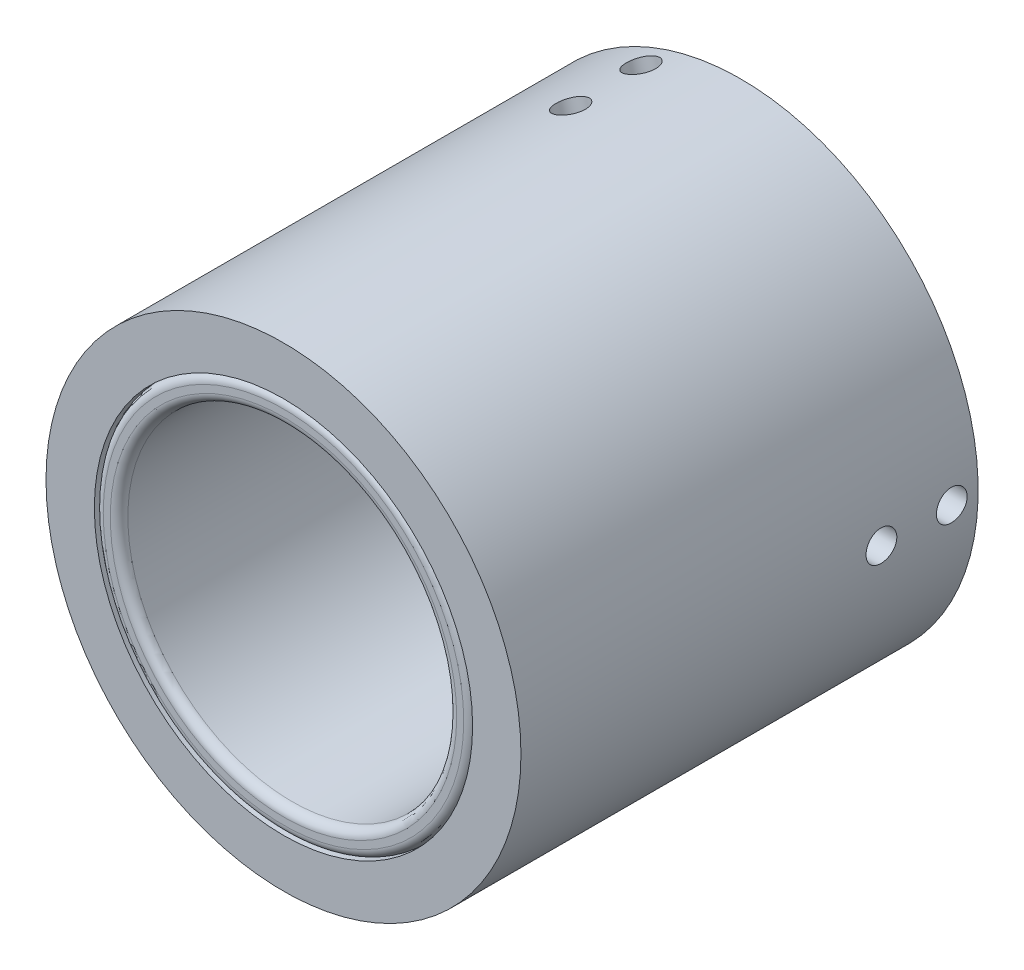
SolidWorks part; units mm, degrees
ref_plane "Plan de face" through (0, 0, 0) normal (0, 0, 1) x (1, 0, 0)
ref_plane "Plan de dessus" through (0, 0, 0) normal (0, 1, 0) x (1, 0, 0)
ref_plane "Plan de droite" through (0, 0, 0) normal (1, 0, 0) x (0, 0, -1)
sketch "Esquisse6" plane through (0, 0, 0) normal (0, 0, 1) x (1, 0, 0)
  line L0 (0, 0) -> (4.4539, 28.1206) construction
  line L1 (0, 0) -> (12.5667, 24.6635) construction
  line L2 (0, 0) -> (19.5026, 19.5026) construction
  line L3 (9.7608, 19.1566) -> (10.8958, 21.3842)
  line L4 (16.9706, 16.9706) -> (15.2028, 15.2028)
  line L5 (19.1566, 9.7608) -> (21.3842, 10.8958)
  line L6 (23.7045, 3.7544) -> (21.2353, 3.3633)
  line L7 (21.2353, -3.3633) -> (23.7045, -3.7544)
  line L8 (21.3842, -10.8958) -> (19.1566, -9.7608)
  line L9 (15.2028, -15.2028) -> (16.9706, -16.9706)
  line L10 (10.8958, -21.3842) -> (9.7608, -19.1566)
  line L11 (3.3633, -21.2353) -> (3.7544, -23.7045)
  line L12 (-3.7544, -23.7045) -> (-3.3633, -21.2353)
  line L13 (-9.7608, -19.1566) -> (-10.8958, -21.3842)
  line L14 (-16.9706, -16.9706) -> (-15.2028, -15.2028)
  line L15 (-19.1566, -9.7608) -> (-21.3842, -10.8958)
  line L16 (-23.7045, -3.7544) -> (-21.2353, -3.3633)
  line L17 (-21.2353, 3.3633) -> (-23.7045, 3.7544)
  line L18 (-21.3842, 10.8958) -> (-19.1566, 9.7608)
  line L19 (-15.2028, 15.2028) -> (-16.9706, 16.9706)
  line L20 (-10.8958, 21.3842) -> (-9.7608, 19.1566)
  line L21 (-3.3633, 21.2353) -> (-3.7544, 23.7045)
  line L22 (3.7544, 23.7045) -> (3.3633, 21.2353)
  line L23 (-10.8958, 21.3842) -> (10.8958, -21.3842) construction
  line L24 (0, 0) -> (0, 33.4225) construction
  line L25 (21.3842, 10.8958) -> (-21.3842, -10.8958) construction
  line L26 (23.7045, 3.7544) -> (-23.7045, -3.7544) construction
  line L27 (23.7045, -3.7544) -> (-23.7045, 3.7544) construction
  line L28 (21.3842, -10.8958) -> (-21.3842, 10.8958) construction
  line L29 (16.9706, -16.9706) -> (-16.9706, 16.9706) construction
  line L30 (3.7544, -23.7045) -> (-3.7544, 23.7045) construction
  line L31 (-3.7544, -23.7045) -> (0, 0) construction
  line L32 (-10.8958, -21.3842) -> (0, 0) construction
  line L33 (-16.9706, -16.9706) -> (0, 0) construction
  circle A0 centre (0, 0) radius 25 construction
  circle A1 centre (0, 0) radius 24 construction
  circle A2 centre (0, 0) radius 21.5 construction
  arc A3 (3.3633, 21.2353) -> (9.7608, 19.1566) centre (0, 0) cw
  arc A4 (10.8958, 21.3842) -> (16.9706, 16.9706) centre (0, 0) cw
  arc A5 (15.2028, 15.2028) -> (19.1566, 9.7608) centre (0, 0) cw
  arc A6 (21.3842, 10.8958) -> (23.7045, 3.7544) centre (0, 0) cw
  arc A7 (21.2353, 3.3633) -> (21.2353, -3.3633) centre (0, 0) cw
  arc A8 (23.7045, -3.7544) -> (21.3842, -10.8958) centre (0, 0) cw
  arc A9 (19.1566, -9.7608) -> (15.2028, -15.2028) centre (0, 0) cw
  arc A10 (16.9706, -16.9706) -> (10.8958, -21.3842) centre (0, 0) cw
  arc A11 (9.7608, -19.1566) -> (3.3633, -21.2353) centre (0, 0) cw
  arc A12 (3.7544, -23.7045) -> (-3.7544, -23.7045) centre (0, 0) cw
  arc A13 (-3.3633, -21.2353) -> (-9.7608, -19.1566) centre (0, 0) cw
  arc A14 (-10.8958, -21.3842) -> (-16.9706, -16.9706) centre (0, 0) cw
  arc A15 (-15.2028, -15.2028) -> (-19.1566, -9.7608) centre (0, 0) cw
  arc A16 (-21.3842, -10.8958) -> (-23.7045, -3.7544) centre (0, 0) cw
  arc A17 (-21.2353, -3.3633) -> (-21.2353, 3.3633) centre (0, 0) cw
  arc A18 (-23.7045, 3.7544) -> (-21.3842, 10.8958) centre (0, 0) cw
  arc A19 (-19.1566, 9.7608) -> (-15.2028, 15.2028) centre (0, 0) cw
  arc A20 (-16.9706, 16.9706) -> (-10.8958, 21.3842) centre (0, 0) cw
  arc A21 (-9.7608, 19.1566) -> (-3.3633, 21.2353) centre (0, 0) cw
  arc A22 (-3.7544, 23.7045) -> (3.7544, 23.7045) centre (0, 0) cw
  circle A23 centre (0, 0) radius 3.025
  circle A24 centre (0, 0) radius 9.025 construction
  circle A25 centre (0, 0) radius 17.5 construction
  point P62 (0, 0)
  dimension "D1" = 50
  dimension "D4" = 2.5
  dimension "D5" = 48
  dimension "D7" = 6.05
  dimension "D9" = 6
  dimension "D10" = 4
  dimension "D2" = 18
  dimension "D3" = 18
  dimension "D8" = 9
  dimension "D6" = 10
extrude "Jante" add sketch "Esquisse6" along normal blind 46 from offset 20
sketch "Esquisse8" plane through (0, 0, 66) normal (0, 0, 1) x (1, 0, 0)
  circle A0 centre (0, 0) radius 21.5
  circle A1 centre (0, 0) radius 3.025
  circle A2 centre (0, 0) radius 3.025 construction
  arc A3 (-15.2028, 15.2028) -> (-19.1566, 9.7608) centre (0, 0) ccw construction
extrude "Boss.-Extru.5" add sketch "Esquisse8" along normal blind 3
sketch "Esquisse9" plane through (0, 0, 20) normal (0, 0, -1) x (-1, 0, 0)
  circle A0 centre (0, 0) radius 21.5
  circle A1 centre (0, 0) radius 3.025
  arc A2 (19.1566, 9.7608) -> (15.2028, 15.2028) centre (0, 0) ccw construction
  circle A3 centre (0, 0) radius 3.025 construction
extrude "Boss.-Extru.6" add sketch "Esquisse9" along normal blind 3
sketch "Esquisse7" plane through (0, 0, 0) normal (0, 0, 1) x (1, 0, 0)
  line L40 (-9.7564, 19.1701) -> (-10.8914, 21.3976)
  line L41 (-16.9847, 16.9706) -> (-15.2169, 15.2028)
  line L42 (-19.161, 9.7742) -> (-21.3885, 10.9092)
  line L43 (-23.716, 3.7461) -> (-21.2467, 3.355)
  line L44 (-21.2467, -3.355) -> (-23.716, -3.7461)
  line L45 (-21.3885, -10.9092) -> (-19.161, -9.7742)
  line L46 (-15.2169, -15.2028) -> (-16.9847, -16.9706)
  line L47 (-10.8914, -21.3976) -> (-9.7564, -19.1701)
  line L48 (-3.3748, -21.2436) -> (-3.7659, -23.7128)
  line L49 (3.7659, -23.7128) -> (3.3748, -21.2436)
  line L50 (9.7564, -19.1701) -> (10.8914, -21.3976)
  line L51 (16.9847, -16.9706) -> (15.2169, -15.2028)
  line L52 (19.161, -9.7742) -> (21.3885, -10.9092)
  line L53 (23.716, -3.7461) -> (21.2467, -3.355)
  line L54 (21.2467, 3.355) -> (23.716, 3.7461)
  line L55 (21.3885, 10.9092) -> (19.161, 9.7742)
  line L56 (15.2169, 15.2028) -> (16.9847, 16.9706)
  line L57 (10.8914, 21.3976) -> (9.7564, 19.1701)
  line L58 (3.3748, 21.2436) -> (3.7659, 23.7128)
  line L59 (-3.7659, 23.7128) -> (-3.3748, 21.2436)
  line L60 (-9.7564, 19.1701) -> (-10.8914, 21.3976)
  line L61 (-16.9847, 16.9706) -> (-15.2169, 15.2028)
  line L62 (-19.161, 9.7742) -> (-21.3885, 10.9092)
  line L63 (-23.716, 3.7461) -> (-21.2467, 3.355)
  line L64 (-21.2467, -3.355) -> (-23.716, -3.7461)
  line L65 (-21.3885, -10.9092) -> (-19.161, -9.7742)
  line L66 (-15.2169, -15.2028) -> (-16.9847, -16.9706)
  line L67 (-10.8914, -21.3976) -> (-9.7564, -19.1701)
  line L68 (-3.3748, -21.2436) -> (-3.7659, -23.7128)
  line L69 (3.7659, -23.7128) -> (3.3748, -21.2436)
  line L70 (9.7564, -19.1701) -> (10.8914, -21.3976)
  line L71 (16.9847, -16.9706) -> (15.2169, -15.2028)
  line L72 (19.161, -9.7742) -> (21.3885, -10.9092)
  line L73 (23.716, -3.7461) -> (21.2467, -3.355)
  line L74 (21.2467, 3.355) -> (23.716, 3.7461)
  line L75 (21.3885, 10.9092) -> (19.161, 9.7742)
  line L76 (15.2169, 15.2028) -> (16.9847, 16.9706)
  line L77 (10.8914, 21.3976) -> (9.7564, 19.1701)
  line L78 (3.3748, 21.2436) -> (3.7659, 23.7128)
  line L79 (-3.7659, 23.7128) -> (-3.3748, 21.2436)
  circle A20 centre (0, 0) radius 27.01
  arc A40 (-3.3748, 21.2436) -> (-9.7564, 19.1701) centre (0, 0) ccw
  arc A41 (-10.8914, 21.3976) -> (-16.9847, 16.9706) centre (0, 0) ccw
  arc A42 (-15.2169, 15.2028) -> (-19.161, 9.7742) centre (0, 0) ccw
  arc A43 (-21.3885, 10.9092) -> (-23.716, 3.7461) centre (0, 0) ccw
  arc A44 (-21.2467, 3.355) -> (-21.2467, -3.355) centre (0, 0) ccw
  arc A45 (-23.716, -3.7461) -> (-21.3885, -10.9092) centre (0, 0) ccw
  arc A46 (-19.161, -9.7742) -> (-15.2169, -15.2028) centre (0, 0) ccw
  arc A47 (-16.9847, -16.9706) -> (-10.8914, -21.3976) centre (0, 0) ccw
  arc A48 (-9.7564, -19.1701) -> (-3.3748, -21.2436) centre (0, 0) ccw
  arc A49 (-3.7659, -23.7128) -> (3.7659, -23.7128) centre (0, 0) ccw
  arc A50 (3.3748, -21.2436) -> (9.7564, -19.1701) centre (0, 0) ccw
  arc A51 (10.8914, -21.3976) -> (16.9847, -16.9706) centre (0, 0) ccw
  arc A52 (15.2169, -15.2028) -> (19.161, -9.7742) centre (0, 0) ccw
  arc A53 (21.3885, -10.9092) -> (23.716, -3.7461) centre (0, 0) ccw
  arc A54 (21.2467, -3.355) -> (21.2467, 3.355) centre (0, 0) ccw
  arc A55 (23.716, 3.7461) -> (21.3885, 10.9092) centre (0, 0) ccw
  arc A56 (19.161, 9.7742) -> (15.2169, 15.2028) centre (0, 0) ccw
  arc A57 (16.9847, 16.9706) -> (10.8914, 21.3976) centre (0, 0) ccw
  arc A58 (9.7564, 19.1701) -> (3.3748, 21.2436) centre (0, 0) ccw
  arc A59 (3.7659, 23.7128) -> (-3.7659, 23.7128) centre (0, 0) ccw
  arc A60 (-3.3748, 21.2436) -> (-9.7564, 19.1701) centre (0, 0) ccw
  arc A61 (-10.8914, 21.3976) -> (-16.9847, 16.9706) centre (0, 0) ccw
  arc A62 (-15.2169, 15.2028) -> (-19.161, 9.7742) centre (0, 0) ccw
  arc A63 (-21.3885, 10.9092) -> (-23.716, 3.7461) centre (0, 0) ccw
  arc A64 (-21.2467, 3.355) -> (-21.2467, -3.355) centre (0, 0) ccw
  arc A65 (-23.716, -3.7461) -> (-21.3885, -10.9092) centre (0, 0) ccw
  arc A66 (-19.161, -9.7742) -> (-15.2169, -15.2028) centre (0, 0) ccw
  arc A67 (-16.9847, -16.9706) -> (-10.8914, -21.3976) centre (0, 0) ccw
  arc A68 (-9.7564, -19.1701) -> (-3.3748, -21.2436) centre (0, 0) ccw
  arc A69 (-3.7659, -23.7128) -> (3.7659, -23.7128) centre (0, 0) ccw
  arc A70 (3.3748, -21.2436) -> (9.7564, -19.1701) centre (0, 0) ccw
  arc A71 (10.8914, -21.3976) -> (16.9847, -16.9706) centre (0, 0) ccw
  arc A72 (15.2169, -15.2028) -> (19.161, -9.7742) centre (0, 0) ccw
  arc A73 (21.3885, -10.9092) -> (23.716, -3.7461) centre (0, 0) ccw
  arc A74 (21.2467, -3.355) -> (21.2467, 3.355) centre (0, 0) ccw
  arc A75 (23.716, 3.7461) -> (21.3885, 10.9092) centre (0, 0) ccw
  arc A76 (19.161, 9.7742) -> (15.2169, 15.2028) centre (0, 0) ccw
  arc A77 (16.9847, 16.9706) -> (10.8914, 21.3976) centre (0, 0) ccw
  arc A78 (9.7564, 19.1701) -> (3.3748, 21.2436) centre (0, 0) ccw
  arc A79 (3.7659, 23.7128) -> (-3.7659, 23.7128) centre (0, 0) ccw
  dimension "D2" = 3
  dimension "D1" = 0.01
extrude "Pneu" add sketch "Esquisse7" along normal up to surface (66 mm away) from offset 20 separate body up to face at (-13.2898, 18.2918, 66)
sketch "Esquisse10" plane through (0, 0, 66) normal (0, 0, 1) x (1, 0, 0)
  circle A1 centre (0, 0) radius 27.01
  circle A3 centre (0, 0) radius 21.51
  circle A4 centre (0, 0) radius 27.01 construction
  arc A5 (-9.7564, -19.1701) -> (-3.3748, -21.2436) centre (0, 0) ccw construction
extrude "Boss.-Extru.7" add sketch "Esquisse10" along normal blind 3
sketch "Esquisse11" plane through (0, 0, 20) normal (0, 0, -1) x (-1, 0, 0)
  circle A0 centre (0, 0) radius 21.51
  circle A1 centre (0, 0) radius 27.01
  circle A2 centre (0, 0) radius 27.01 construction
  arc A3 (19.161, 9.7742) -> (15.2169, 15.2028) centre (0, 0) ccw construction
extrude "Boss.-Extru.8" add sketch "Esquisse11" along normal blind 3
sketch "Esquisse15" plane through (0, 0, 17) normal (0, 0, -1) x (-1, 0, 0)
  line L0 (0, 0) -> (26.1385, -8.4929) construction
  line L1 (42.5408, 0) -> (0, 0) construction
  dimension "D1" = 18
ref_plane "Plan1" through (0, 0, 0) normal (0.309, -0.9511, 0) x (-0.9511, -0.309, 0)
sketch "Esquisse5" plane through (0, 0, 0) normal (0.309, -0.9511, 0) x (0, 0, -1)
  line L0 (-17, -27.01) -> (-17, 27.01) construction
  circle A0 centre (4, 0) radius 1.75
  circle A1 centre (-20, 0) radius 1.75
  circle A2 centre (-28, 0) radius 1.75
  dimension "D2" = 3.5
  dimension "D5" = 3.5
  dimension "D6" = 3.5
  dimension "D1" = 4
  dimension "D3" = 3
  dimension "D4" = 8
extrude "Enlèv. mat.-Extru.2" cut sketch "Esquisse5" against normal through all and the other way through all
sketch "Esquisse4" plane through (0, 0, 0) normal (1, 0, 0) x (0, -1, 0)
  line L1 (27.01, -17) -> (-27.01, -17) construction
  circle A0 centre (0, 4) radius 1.75
  circle A1 centre (0, -20) radius 1.75
  circle A2 centre (0, -28) radius 1.75
  dimension "D2" = 3.5
  dimension "D6" = 3.5
  dimension "D1" = 4
  dimension "D3" = 8
  dimension "D5" = 3
extrude "Enlèv. mat.-Extru.1" cut sketch "Esquisse4" against normal through all and the other way through all
sketch "Esquisse12" plane through (0, 0, 69) normal (0, 0, 1) x (1, 0, 0)
  line L0 (-6.3816, 6.3816) -> (-7.9448, 15.5926)
  line L3 (4.0973, 8.0413) -> (12.3744, 12.3744)
  line L5 (-17.2845, 2.7376) -> (-8.0413, 4.0973)
  line L7 (-8.0413, 4.0973) -> (-6.3816, 6.3816)
  line L8 (-2.7376, 17.2845) -> (1.4118, 8.9139)
  line L9 (1.4118, 8.9139) -> (4.0973, 8.0413)
  line L10 (8.9139, -1.4118) -> (15.5926, -7.9448)
  line L11 (15.5926, 7.9448) -> (8.9139, 1.4118)
  line L12 (8.9139, 1.4118) -> (8.9139, -1.4118)
  line L13 (1.4118, -8.9139) -> (-2.7376, -17.2845)
  line L14 (12.3744, -12.3744) -> (4.0973, -8.0413)
  line L15 (4.0973, -8.0413) -> (1.4118, -8.9139)
  line L16 (-8.0413, -4.0973) -> (-17.2845, -2.7376)
  line L17 (-7.9448, -15.5926) -> (-6.3816, -6.3816)
  line L18 (-6.3816, -6.3816) -> (-8.0413, -4.0973)
  line L19 (21.3842, -10.8958) -> (-21.3842, 10.8958) construction
  line L20 (16.9706, -16.9706) -> (-16.9706, 16.9706) construction
  line L21 (23.7045, -3.7544) -> (-23.7045, 3.7544) construction
  line L22 (-10.8958, 21.3842) -> (10.8958, -21.3842) construction
  circle A0 centre (0, 0) radius 9.025 construction
  circle A1 centre (0, 0) radius 17.5 construction
  arc A4 (-17.2845, 2.7376) -> (-7.9448, 15.5926) centre (0, 0) cw
  arc A5 (-2.7376, 17.2845) -> (12.3744, 12.3744) centre (0, 0) cw
  arc A6 (15.5926, 7.9448) -> (15.5926, -7.9448) centre (0, 0) cw
  arc A7 (12.3744, -12.3744) -> (-2.7376, -17.2845) centre (0, 0) cw
  arc A8 (-7.9448, -15.5926) -> (-17.2845, -2.7376) centre (0, 0) cw
  point P2 (0, 0)
  point P3 (0, 0)
  point P4 (0, 0)
  point P7 (0, 0)
  point P14 (0, 0)
  point P18 (0, 0)
  point P36 (0, 0)
  point P39 (0, 0)
  dimension "D1" = 5
extrude "Enlèv. mat.-Extru.7" cut sketch "Esquisse12" against normal through all
sketch "Esquisse13" plane through (0, 0, 69) normal (0, 0, -1) x (-1, 0, 0)
  circle A0 centre (0, 0) radius 18.7
  dimension "D1" = 37.4
extrude "Enlèv. mat.-Extru.9" cut sketch "Esquisse13" along normal offset from surface (37.2 mm away) 14.8 up to face at (-10.2989, -7.4826, 17)
sketch "Esquisse14" plane through (0, 0, 17) normal (0, 0, -1) x (-1, 0, 0)
  circle A0 centre (0, 0) radius 21.5
  circle A1 centre (0, 0) radius 34.9398
extrude "Enlèv. mat.-Extru.10" cut sketch "Esquisse14" against normal blind 22 from offset 15 offset against normal yes
fillet "Congé1" radius 1 104 edges at (21.5, 0, 69) (-18.7, 0, 69) (-3.025, 0, 17) (-21.5, 0, 17) (-12.6629, 3.4174, 17) (-14.1578, 10.2862, 17) (-7.1632, 10.9871, 17) (-7.2115, 5.2395, 17) (-0.6629, 13.0992, 17) (5.4078, 16.6435, 17) (8.2358, 10.2079, 17) (2.7545, 8.4776, 17) (12.2533, 4.6783, 17) (17.5, 0, 17) (12.2533, -4.6783, 17) (8.9139, 0, 17) (8.2358, -10.2079, 17) (5.4078, -16.6435, 17) (-0.6629, -13.0992, 17) (2.7545, -8.4776, 17) (-7.1632, -10.9871, 17) (-14.1578, -10.2862, 17) (-12.6629, -3.4174, 17) (-7.2115, -5.2395, 17) (21.3842, -10.8958, 60) (21.3842, -10.8958, 26) (22.8254, -7.4164, 66) (23.7045, -3.7544, 60) (23.7045, -3.7544, 26) (22.8254, -7.4164, 20) (10.8958, -21.3842, 60) (10.8958, -21.3842, 26) (14.1068, -19.4164, 66) (16.9706, -16.9706, 60) (16.9706, -16.9706, 26) (14.1068, -19.4164, 20) (-3.7544, -23.7045, 60) (-3.7544, -23.7045, 26) (0, -24, 66) (3.7544, -23.7045, 60) (3.7544, -23.7045, 26) (0, -24, 20) (-16.9706, -16.9706, 60) (-16.9706, -16.9706, 26) (-14.1068, -19.4164, 66) (-10.8958, -21.3842, 60) (-10.8958, -21.3842, 26) (-14.1068, -19.4164, 20) (-23.7045, -3.7544, 60) (-23.7045, -3.7544, 26) (-22.8254, -7.4164, 66) (-21.3842, -10.8958, 60) (-21.3842, -10.8958, 26) (-22.8254, -7.4164, 20) (-21.3842, 10.8958, 60) (-21.3842, 10.8958, 26) (-22.8254, 7.4164, 66) (-23.7045, 3.7544, 60) (-23.7045, 3.7544, 26) (-22.8254, 7.4164, 20) (23.7045, 3.7544, 60) (23.7045, 3.7544, 26) (22.8254, 7.4164, 66) (21.3842, 10.8958, 60) (21.3842, 10.8958, 26) (22.8254, 7.4164, 20) (16.9706, 16.9706, 60) (16.9706, 16.9706, 26) (14.1068, 19.4164, 66) (10.8958, 21.3842, 60) (10.8958, 21.3842, 26) (14.1068, 19.4164, 20) (3.7544, 23.7045, 60) (3.7544, 23.7045, 26) (0, 24, 66) (-3.7544, 23.7045, 60) (-3.7544, 23.7045, 26) (0, 24, 20) (-10.8958, 21.3842, 60) (-10.8958, 21.3842, 26) (-14.1068, 19.4164, 66) (-16.9706, 16.9706, 60) (-16.9706, 16.9706, 26) (-14.1068, 19.4164, 20) (0, -24, 32) (0, 24, 32) (22.8254, 7.4164, 32) (22.8254, -7.4164, 32) (14.1068, -19.4164, 32) (-14.1068, -19.4164, 32) (-22.8254, -7.4164, 32) (-14.1068, 19.4164, 54) (-22.8254, 7.4164, 54) (-22.8254, -7.4164, 54) (-14.1068, -19.4164, 54) (0, -24, 54) (22.8254, 7.4164, 54) (14.1068, -19.4164, 54) (22.8254, -7.4164, 54) (0, 24, 54) (14.1068, 19.4164, 54) (14.1068, 19.4164, 32) (-22.8254, 7.4164, 32) (-14.1068, 19.4164, 32)
